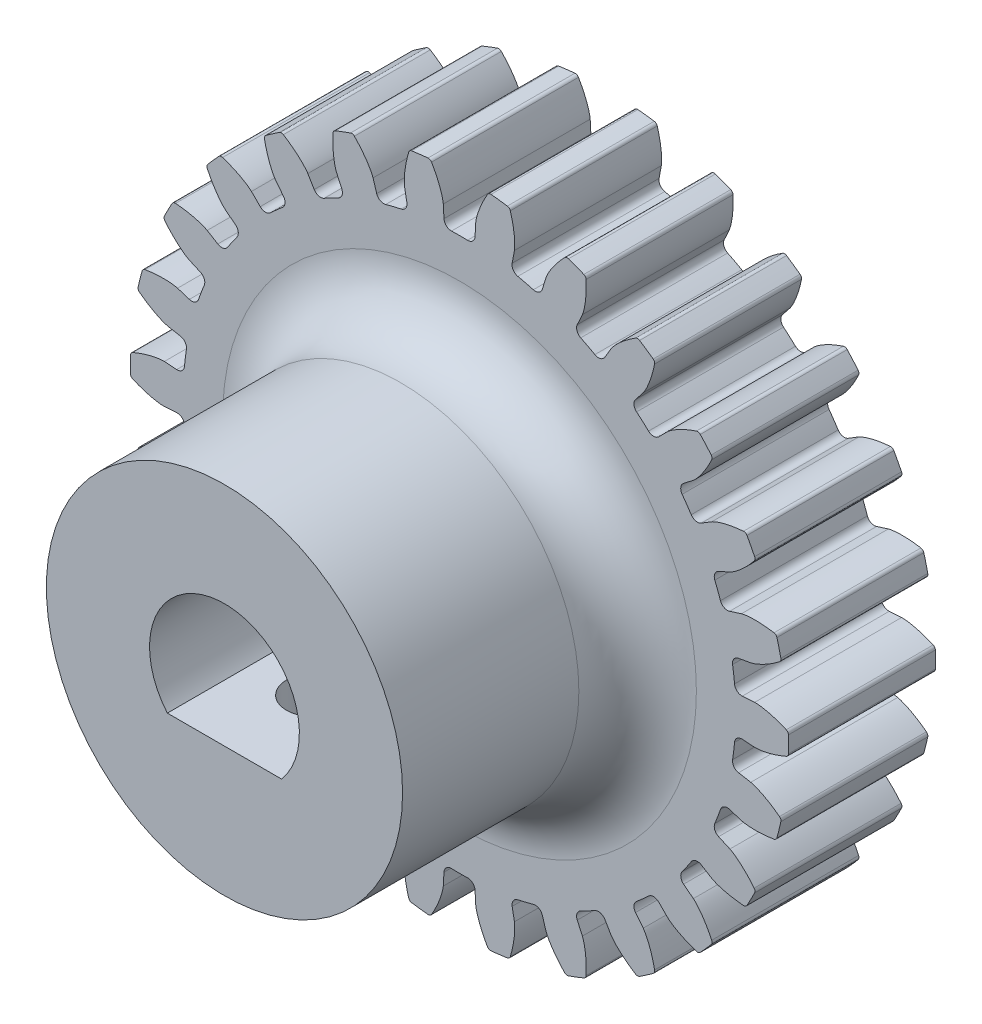
SolidWorks part; units mm, degrees
material "ABS"
ref_plane "Front" through (0, 0, 0) normal (0, 0, 1) x (1, 0, 0)
ref_plane "Top" through (0, 0, 0) normal (0, 1, 0) x (1, 0, 0)
ref_plane "Right" through (0, 0, 0) normal (1, 0, 0) x (0, 0, -1)
sketch "Sketch1" plane through (0, 0, 0) normal (0, 0, 1) x (1, 0, 0)
  circle A0 centre (0, 0) radius 14.224
  dimension "OutsideDiameter" = 28.448
extrude "Boss-Extrude1" add sketch "Sketch1" along normal blind 6.35
sketch "Sketch3" plane through (0, 0, 0) normal (0, 0, 1) x (1, 0, 0)
  line L0 (0, 0) -> (43.7181, 0) construction
  line L2 (0, 0) -> (-0.6547, 11.92) construction
  line L3 (0, 0) -> (0.6547, 11.92) construction
  line L4 (0.6547, 11.92) -> (0.7013, 12.768) construction
  line L5 (0, 0) -> (0, 61.276) construction
  line L6 (-0.6547, 11.92) -> (-0.7013, 12.768) construction
  circle A0 centre (0, 0) radius 14.224 construction
  circle A1 centre (0, 0) radius 13.208 construction
  circle A2 centre (0, 0) radius 12.7873 construction
  arc A3 (0.6547, 11.92) -> (-0.6547, 11.92) centre (0, 0) ccw construction
  arc A5 (1.2601, 14.1681) -> (-1.2601, 14.1681) centre (0, 0) ccw
  spline S0 degree 4 poles (-0.7013, 12.768) (-0.7014, 12.7703) (-0.7019, 12.7766) (-0.7031, 12.7884) (-0.7055, 12.8077) (-0.709, 12.8323) (-0.7143, 12.864) (-0.7215, 12.9013) (-0.7302, 12.9422) (-0.7407, 12.9866) (-0.752, 13.0308) (-0.7641, 13.0749) (-0.777, 13.1187) (-0.7933, 13.1717) (-0.8142, 13.2351) (-0.8403, 13.3091) (-0.872, 13.3928) (-0.9064, 13.4778) (-0.9422, 13.5612) (-0.9804, 13.6452) (-1.0189, 13.7264) (-1.061, 13.8104) (-1.1009, 13.8878) (-1.148, 13.9742) (-1.1867, 14.0438) (-1.2403, 14.1353) (-1.2727, 14.1892) (-1.3115, 14.2522) (-1.3292, 14.2801) (-1.3401, 14.2973) knots 0 0 0 0 0 0.005377 0.015084 0.028532 0.04661 0.064855 0.092111 0.119476 0.146842 0.174209 0.201575 0.228941 0.256307 0.307035 0.361767 0.4165 0.471232 0.525964 0.580697 0.635429 0.690161 0.744894 0.799626 0.854358 0.909091 0.954545 1 1 1 1 1 construction
  spline S1 degree 4 poles (-0.7013, 12.768) (-0.7014, 12.7703) (-0.7019, 12.7766) (-0.7031, 12.7884) (-0.7055, 12.8077) (-0.709, 12.8323) (-0.7143, 12.864) (-0.7215, 12.9013) (-0.7302, 12.9422) (-0.7407, 12.9866) (-0.752, 13.0308) (-0.7641, 13.0749) (-0.777, 13.1187) (-0.7933, 13.1717) (-0.8142, 13.2351) (-0.8403, 13.3091) (-0.872, 13.3928) (-0.9064, 13.4778) (-0.9422, 13.5612) (-0.9804, 13.6452) (-1.0189, 13.7264) (-1.061, 13.8104) (-1.1009, 13.8878) (-1.148, 13.9742) (-1.1867, 14.0438) (-1.2287, 14.1154) (-1.2494, 14.1503) (-1.2601, 14.1681) knots 0 0 0 0 0 0.005377 0.015084 0.028532 0.04661 0.064855 0.092111 0.119476 0.146842 0.174209 0.201575 0.228941 0.256307 0.307035 0.361767 0.4165 0.471232 0.525964 0.580697 0.635429 0.690161 0.744894 0.799626 0.854358 0.909091 0.909091 0.909091 0.909091 0.909091
  spline S2 degree 4 poles (0.7013, 12.768) (0.7014, 12.7703) (0.7019, 12.7766) (0.7031, 12.7884) (0.7055, 12.8077) (0.709, 12.8323) (0.7143, 12.864) (0.7215, 12.9013) (0.7302, 12.9422) (0.7407, 12.9866) (0.752, 13.0308) (0.7641, 13.0749) (0.777, 13.1187) (0.7933, 13.1717) (0.8142, 13.2351) (0.8403, 13.3091) (0.872, 13.3928) (0.9064, 13.4778) (0.9422, 13.5612) (0.9804, 13.6452) (1.0189, 13.7264) (1.061, 13.8104) (1.1009, 13.8878) (1.148, 13.9742) (1.1867, 14.0438) (1.2403, 14.1353) (1.2727, 14.1892) (1.3115, 14.2522) (1.3292, 14.2801) (1.3401, 14.2973) knots 0 0 0 0 0 0.005377 0.015084 0.028532 0.04661 0.064855 0.092111 0.119476 0.146842 0.174209 0.201575 0.228941 0.256307 0.307035 0.361767 0.4165 0.471232 0.525964 0.580697 0.635429 0.690161 0.744894 0.799626 0.854358 0.909091 0.954545 1 1 1 1 1 construction
  spline S3 degree 4 poles (0.7013, 12.768) (0.7014, 12.7703) (0.7019, 12.7766) (0.7031, 12.7884) (0.7055, 12.8077) (0.709, 12.8323) (0.7143, 12.864) (0.7215, 12.9013) (0.7302, 12.9422) (0.7407, 12.9866) (0.752, 13.0308) (0.7641, 13.0749) (0.777, 13.1187) (0.7933, 13.1717) (0.8142, 13.2351) (0.8403, 13.3091) (0.872, 13.3928) (0.9064, 13.4778) (0.9422, 13.5612) (0.9804, 13.6452) (1.0189, 13.7264) (1.061, 13.8104) (1.1009, 13.8878) (1.148, 13.9742) (1.1867, 14.0438) (1.2287, 14.1154) (1.2494, 14.1503) (1.2601, 14.1681) knots 0 0 0 0 0 0.005377 0.015084 0.028532 0.04661 0.064855 0.092111 0.119476 0.146842 0.174209 0.201575 0.228941 0.256307 0.307035 0.361767 0.4165 0.471232 0.525964 0.580697 0.635429 0.690161 0.744894 0.799626 0.854358 0.909091 0.909091 0.909091 0.909091 0.909091
  point P0 (0, 11.938)
  dimension "OutsideDiameter" = 28.448
  dimension "PitchCircle" = 26.416
  dimension "BaseCircle" = 25.5746
  dimension "DedendumCircle" = 23.876
sketch "DCLTBC" plane through (0, 0, 0) normal (0, 0, 1) x (1, 0, 0)
  line L0 (0, 0) -> (41.04, 0) construction
  line L1 (-0.6547, 11.92) -> (-0.7013, 12.768) construction
  line L2 (0.6547, 11.92) -> (0.7013, 12.768) construction
  line L3 (-0.6547, 11.92) -> (-0.7013, 12.768)
  line L4 (0.6547, 11.92) -> (0.7013, 12.768)
  line L5 (0, 0) -> (0, 104.9356) construction
  circle A0 centre (0, 0) radius 14.224
  circle A1 centre (0, 0) radius 13.208 construction
  circle A2 centre (0, 0) radius 12.7873 construction
  arc A3 (0.6547, 11.92) -> (-0.6547, 11.92) centre (0, 0) ccw construction
  arc A4 (0.6547, 11.92) -> (-0.6547, 11.92) centre (0, 0) ccw
  spline S0 degree 4 poles (-997.5218, -66.5121) (-10.52, 11.3394) (-0.7979, 12.1584) (-0.6668, 12.4893) (-0.7055, 12.8077) (-0.709, 12.8323) (-0.7143, 12.864) (-0.7215, 12.9013) (-0.7302, 12.9422) (-0.7407, 12.9866) (-0.752, 13.0308) (-0.7641, 13.0749) (-0.777, 13.1187) (-0.7933, 13.1717) (-0.8142, 13.2351) (-0.8403, 13.3091) (-0.872, 13.3928) (-0.9064, 13.4778) (-0.9422, 13.5612) (-0.9804, 13.6452) (-1.0189, 13.7264) (-1.061, 13.8104) (-1.1009, 13.8878) (-1.148, 13.9742) (-1.3672, 14.3683) (-2.2498, 15.7567) (10.602, -5.7239) (-517.3013, 870.6887) knots -0.722064 -0.722064 -0.722064 -0.722064 -0.722064 0.005377 0.015084 0.028532 0.04661 0.064855 0.092111 0.119476 0.146842 0.174209 0.201575 0.228941 0.256307 0.307035 0.361767 0.4165 0.471232 0.525964 0.580697 0.635429 0.690161 0.744894 0.799626 0.854358 1.929512 1.929512 1.929512 1.929512 1.929512 only from (-0.7013, 12.768) to (-1.2601, 14.1681) construction
  spline S1 degree 4 poles (997.5218, -66.5121) (10.52, 11.3394) (0.7979, 12.1584) (0.6668, 12.4893) (0.7055, 12.8077) (0.709, 12.8323) (0.7143, 12.864) (0.7215, 12.9013) (0.7302, 12.9422) (0.7407, 12.9866) (0.752, 13.0308) (0.7641, 13.0749) (0.777, 13.1187) (0.7933, 13.1717) (0.8142, 13.2351) (0.8403, 13.3091) (0.872, 13.3928) (0.9064, 13.4778) (0.9422, 13.5612) (0.9804, 13.6452) (1.0189, 13.7264) (1.061, 13.8104) (1.1009, 13.8878) (1.148, 13.9742) (1.3672, 14.3683) (2.2498, 15.7567) (-10.602, -5.7239) (517.3013, 870.6887) knots -0.722064 -0.722064 -0.722064 -0.722064 -0.722064 0.005377 0.015084 0.028532 0.04661 0.064855 0.092111 0.119476 0.146842 0.174209 0.201575 0.228941 0.256307 0.307035 0.361767 0.4165 0.471232 0.525964 0.580697 0.635429 0.690161 0.744894 0.799626 0.854358 1.929512 1.929512 1.929512 1.929512 1.929512 only from (0.7013, 12.768) to (1.2601, 14.1681) construction
  spline S2 degree 4 poles (-0.7013, 12.768) (-0.7014, 12.7703) (-0.7019, 12.7766) (-0.7031, 12.7884) (-0.7055, 12.8077) (-0.709, 12.8323) (-0.7143, 12.864) (-0.7215, 12.9013) (-0.7302, 12.9422) (-0.7407, 12.9866) (-0.752, 13.0308) (-0.7641, 13.0749) (-0.777, 13.1187) (-0.7933, 13.1717) (-0.8142, 13.2351) (-0.8403, 13.3091) (-0.872, 13.3928) (-0.9064, 13.4778) (-0.9422, 13.5612) (-0.9804, 13.6452) (-1.0189, 13.7264) (-1.061, 13.8104) (-1.1009, 13.8878) (-1.148, 13.9742) (-1.1867, 14.0438) (-1.2287, 14.1154) (-1.2494, 14.1503) (-1.2601, 14.1681) knots 0 0 0 0 0 0.005377 0.015084 0.028532 0.04661 0.064855 0.092111 0.119476 0.146842 0.174209 0.201575 0.228941 0.256307 0.307035 0.361767 0.4165 0.471232 0.525964 0.580697 0.635429 0.690161 0.744894 0.799626 0.854358 0.909091 0.909091 0.909091 0.909091 0.909091
  spline S3 degree 4 poles (0.7013, 12.768) (0.7014, 12.7703) (0.7019, 12.7766) (0.7031, 12.7884) (0.7055, 12.8077) (0.709, 12.8323) (0.7143, 12.864) (0.7215, 12.9013) (0.7302, 12.9422) (0.7407, 12.9866) (0.752, 13.0308) (0.7641, 13.0749) (0.777, 13.1187) (0.7933, 13.1717) (0.8142, 13.2351) (0.8403, 13.3091) (0.872, 13.3928) (0.9064, 13.4778) (0.9422, 13.5612) (0.9804, 13.6452) (1.0189, 13.7264) (1.061, 13.8104) (1.1009, 13.8878) (1.148, 13.9742) (1.1867, 14.0438) (1.2287, 14.1154) (1.2494, 14.1503) (1.2601, 14.1681) knots 0 0 0 0 0 0.005377 0.015084 0.028532 0.04661 0.064855 0.092111 0.119476 0.146842 0.174209 0.201575 0.228941 0.256307 0.307035 0.361767 0.4165 0.471232 0.525964 0.580697 0.635429 0.690161 0.744894 0.799626 0.854358 0.909091 0.909091 0.909091 0.909091 0.909091
  dimension "OutsideDiameter" = 28.448
  dimension "PitchCircle" = 26.416
  dimension "BaseCircle" = 25.5746
extrude "Cut-Extrude-DCLTBC" cut sketch "DCLTBC" along normal through all contours L4 S3 A0 S2 L3 A4 region at (0, 13.2044, 0)
fillet "Fillet-Tip-DCLTBC" radius 0.1588 2 edges at (1.2601, 14.1681, 3.175) (-1.2601, 14.1681, 3.175)
fillet "Fillet-Root-DCLTBC" radius 0.3176 2 edges at (-0.6547, 11.92, 3.175) (0.6547, 11.92, 3.175)
pattern_circular "CirPattern-DCLTBC" count 26 over 360 about axis through (0, 0, 6.35) along (0, 0, 1) of "Cut-Extrude-DCLTBC", "Fillet-Tip-DCLTBC", "Fillet-Root-DCLTBC"
sketch "DCGTBC" [suppressed] plane through (0, 0, 0) normal (0, 0, 1) x (1, 0, 0)
  line L0 (0, 0) -> (41.04, 0) construction
  line L1 (-37.3224, 3.2653) -> (0, 0) construction
  line L2 (0, 0) -> (37.3224, 3.2653) construction
  line L3 (0, 0) -> (-16.5124, 0)
  line L5 (0, 0) -> (0, 104.9356) construction
  circle A0 centre (0, 0) radius 38.608
  circle A1 centre (0, 0) radius 38.1 construction
  circle A2 centre (0, 0) radius 36.8864 construction
  arc A3 (0.1846, 37.4645) -> (-0.1846, 37.4645) centre (0, 0) ccw construction
  arc A11 (37.3224, 3.2653) -> (-37.3224, 3.2653) centre (0, 0) ccw
  spline S4 degree 4 poles (999.1092, -9.1639) (9.2917, 35.7604) (0.2917, 36.1338) (0.1647, 36.5321) (0.1834, 36.9323) (0.1852, 36.961) (0.188, 36.9982) (0.192, 37.0421) (0.197, 37.0904) (0.2032, 37.143) (0.21, 37.1956) (0.2175, 37.2482) (0.2254, 37.3006) (0.2357, 37.3641) (0.2489, 37.4405) (0.2657, 37.53) (0.2863, 37.6318) (0.309, 37.7359) (0.3327, 37.8385) (0.3583, 37.9426) (0.3842, 38.0436) (0.4127, 38.1489) (0.4399, 38.2463) (0.4722, 38.3558) (0.6183, 38.8417) (1.2009, 40.5477) (-6.8048, 15.7351) (309.5446, 989.6637) knots -0.780323 -0.780323 -0.780323 -0.780323 -0.780323 0.005377 0.015084 0.028532 0.04661 0.064855 0.092111 0.119476 0.146842 0.174209 0.201575 0.228941 0.256307 0.307035 0.361767 0.4165 0.471232 0.525964 0.580697 0.635429 0.690161 0.744894 0.799626 0.854358 1.89102 1.89102 1.89102 1.89102 1.89102 only from (0.1817, 36.886) to (0.5498, 38.6041) construction
  spline S5 degree 4 poles (-999.1092, -9.1639) (-9.2917, 35.7604) (-0.2917, 36.1338) (-0.1647, 36.5321) (-0.1834, 36.9323) (-0.1852, 36.961) (-0.188, 36.9982) (-0.192, 37.0421) (-0.197, 37.0904) (-0.2032, 37.143) (-0.21, 37.1956) (-0.2175, 37.2482) (-0.2254, 37.3006) (-0.2357, 37.3641) (-0.2489, 37.4405) (-0.2657, 37.53) (-0.2863, 37.6318) (-0.309, 37.7359) (-0.3327, 37.8385) (-0.3583, 37.9426) (-0.3842, 38.0436) (-0.4127, 38.1489) (-0.4399, 38.2463) (-0.4722, 38.3558) (-0.6183, 38.8417) (-1.2009, 40.5477) (6.8048, 15.7351) (-309.5446, 989.6637) knots -0.780323 -0.780323 -0.780323 -0.780323 -0.780323 0.005377 0.015084 0.028532 0.04661 0.064855 0.092111 0.119476 0.146842 0.174209 0.201575 0.228941 0.256307 0.307035 0.361767 0.4165 0.471232 0.525964 0.580697 0.635429 0.690161 0.744894 0.799626 0.854358 1.89102 1.89102 1.89102 1.89102 1.89102 only from (-0.1817, 36.886) to (-0.5498, 38.6041) construction
  spline S6 degree 4 poles (0.1817, 36.886) (0.1818, 36.8886) (0.1819, 36.8959) (0.1824, 36.9097) (0.1834, 36.9323) (0.1852, 36.961) (0.188, 36.9982) (0.192, 37.0421) (0.197, 37.0904) (0.2032, 37.143) (0.21, 37.1956) (0.2175, 37.2482) (0.2254, 37.3006) (0.2357, 37.3641) (0.2489, 37.4405) (0.2657, 37.53) (0.2863, 37.6318) (0.309, 37.7359) (0.3327, 37.8385) (0.3583, 37.9426) (0.3842, 38.0436) (0.4127, 38.1489) (0.4399, 38.2463) (0.4722, 38.3558) (0.4989, 38.4444) (0.5279, 38.5364) (0.5423, 38.5812) (0.5498, 38.6041) knots 0 0 0 0 0 0.005377 0.015084 0.028532 0.04661 0.064855 0.092111 0.119476 0.146842 0.174209 0.201575 0.228941 0.256307 0.307035 0.361767 0.4165 0.471232 0.525964 0.580697 0.635429 0.690161 0.744894 0.799626 0.854358 0.909091 0.909091 0.909091 0.909091 0.909091
  spline S7 degree 4 poles (-0.1817, 36.886) (-0.1818, 36.8886) (-0.1819, 36.8959) (-0.1824, 36.9097) (-0.1834, 36.9323) (-0.1852, 36.961) (-0.188, 36.9982) (-0.192, 37.0421) (-0.197, 37.0904) (-0.2032, 37.143) (-0.21, 37.1956) (-0.2175, 37.2482) (-0.2254, 37.3006) (-0.2357, 37.3641) (-0.2489, 37.4405) (-0.2657, 37.53) (-0.2863, 37.6318) (-0.309, 37.7359) (-0.3327, 37.8385) (-0.3583, 37.9426) (-0.3842, 38.0436) (-0.4127, 38.1489) (-0.4399, 38.2463) (-0.4722, 38.3558) (-0.4989, 38.4444) (-0.5279, 38.5364) (-0.5423, 38.5812) (-0.5498, 38.6041) knots 0 0 0 0 0 0.005377 0.015084 0.028532 0.04661 0.064855 0.092111 0.119476 0.146842 0.174209 0.201575 0.228941 0.256307 0.307035 0.361767 0.4165 0.471232 0.525964 0.580697 0.635429 0.690161 0.744894 0.799626 0.854358 0.909091 0.909091 0.909091 0.909091 0.909091
  dimension "D1" = 5
  dimension "D2" = 5
  dimension "OutsideDiameter" = 28.448
  dimension "PitchCircle" = 26.416
  dimension "BaseCircle" = 25.5746
extrude "Cut-Extrude-DCGTBC" [suppressed] cut sketch "DCGTBC" along normal through all
fillet "Fillet-Tip-DCGTBC" [suppressed] radius 0.1588
pattern_circular "CirPattern-DCGTBC" [suppressed] count 26 over 360 of bodies 112
sketch "Sketch4" plane through (0, 0, 6.35) normal (0, 0, 1) x (1, 0, 0)
  line L0 (-2.4692, -2.0955) -> (2.4692, -2.0955)
  arc A0 (2.4692, -2.0955) -> (-2.4692, -2.0955) centre (0, 0) ccw
  circle A1 centre (0, 0) radius 5.1594
  point P3 (0, 3.2385)
  dimension "D1" = 6.477
  dimension "D3" = 10.3187
  dimension "D2" = 5.334
extrude "Cut-Extrude2" cut sketch "Sketch4" against normal through all contours L0 A0 | A1 A0 L0 region at (0, 0.3457, 6.35) region at (-5.0134, 0, 6.35)
sketch "Sketch5" plane through (0, 0, 6.35) normal (0, 0, 1) x (1, 0, 0)
  line L0 (-2.4692, -2.0955) -> (2.4692, -2.0955) construction
  line L1 (-2.4692, -2.0955) -> (2.4692, -2.0955)
  circle A0 centre (0, 0) radius 7.6994
  circle A1 centre (0, 0) radius 5.1594 construction
  arc A2 (2.4692, -2.0955) -> (-2.4692, -2.0955) centre (0, 0) ccw construction
  arc A3 (2.4692, -2.0955) -> (-2.4692, -2.0955) centre (0, 0) ccw
  dimension "D1" = 2.54
extrude "Boss-Extrude2" add sketch "Sketch5" along normal blind 10.16
fillet "Fillet1" radius 2.54 1 edges at (7.6994, 0, 6.35)
ref_plane "Plane1" through (0, -7.6994, 16.51) normal (0, -1, 0) x (-1, 0, 0)
hole_wizard "#4-40 Tapped Hole1" positions "Sketch8" profile "Sketch7" tap size "#4-40" standard "ANSI Inch" end condition up to next
sketch "Sketch8" plane through (0, -7.6994, 16.51) normal (0, -1, 0) x (-1, 0, 0)
  line L0 (0, 0) -> (0, 7.62) construction
  line L2 (-7.6994, 7.62) -> (7.6994, 7.62) construction
  line L3 (-7.6994, 0) -> (7.6994, 0) construction
  point P12 (0, 3.81)
sketch "Sketch7" plane through (0, -7.6994, 12.7) normal (1, 0, 0) x (0, 0, -1)
  line L0 (0, 0) -> (0, 5.6039)
  line L1 (0, 5.6039) -> (1.1303, 5.6039)
  line L2 (1.1303, 5.6039) -> (1.1303, 0.5328)
  line L3 (1.1303, 0.5328) -> (1.7653, 0)
  line L5 (1.7653, 0) -> (0, 0)
  line L6 (-1.1303, 0.5328) -> (-1.7653, 0) construction
  line L11 (0, -6.35) -> (0, 107.95) construction
  dimension "Thru Tap Drill Dia." = 2.2606
  dimension "Thru Tap Drill Depth" = 5.6039
  dimension "Near C'Sink Dia." = 3.5306
  dimension "Near C'Sink Angle" = 100
cosmetic thread "Hole Thread1" parameters "D2"=2.8448
equation "\"DiametralPitch\"= 25'Diametral Pitch"
equation "\"NumTeeth\"= 26'Number of Teeth"
equation "\"PressureAngle\"= 14.5deg'Pressure Angle"
equation "\"Addendum\"= 1 / \"DiametralPitch\"'Addendum"
equation "\"Dedendum\"= 1.25 / \"DiametralPitch\"'Dedendum"
equation "\"WorkingDepth\"= 2 / \"DiametralPitch\"'Working Depth - here for REF (Not used in building model)"
equation "\"WholeDepth\"= 2.25 / \"DiametralPitch\"'Whole Depth - here for REF (Not used in building model)"
equation "\"Clearance\"= .25 / \"DiametralPitch\"'Clearance"
equation "\"CircularPitch\"= pi / \"DiametralPitch\"'Circular Pitch - here for REF (Not used in building model)"
equation "\"PitchCircle\"= \"NumTeeth\" / \"DiametralPitch\"'Pitch Circle - or - Pitch Diameter"
equation "\"OutsideDiameter\"= ( \"NumTeeth\" + 2 ) / \"DiametralPitch\"'Outside Diameter"
equation "\"Fillet_Root\"= \"Clearance\" * cos ( \"PressureAngle\" ) * tan ( ( 90 + \"PressureAngle\" ) / 2 ) 'Fillet Root"
equation "\"AddendumCircle\"= \"PitchCircle\" + ( 2 * \"Addendum\" )'Addendum Circle - or - Addendum Diameter"
equation "\"DedendumCircle\"= \"PitchCircle\" - ( 2 * \"Dedendum\" )'Dedendum Circle - or - Dedendum Diameter"
equation "\"BaseCircle\"= \"PitchCircle\" * cos ( \"PressureAngle\" )'Base Circle - Base Diameter"
equation "\"PitchAngle\"= 360deg / \"NumTeeth\"'Pitch Angle"
equation "\"Alpha\"= sqr ( \"PitchCircle\" ^ 2 - \"BaseCircle\" ^ 2 ) / \"BaseCircle\" * 180 / PI - \"PressureAngle\"'Alpha - Used for Calculating Beta"
equation "\"Beta\"= ( \"PitchAngle\" / 4 - ( \"Alpha\" - 90 ) )'Beta - Used in definition of the parameters for the parametric equation driven curve"
equation "\"Gamma\"= ( \"PitchAngle\" / 4 - ( \"Alpha\" + 90 ) )'Gamma - Used in definition of the parameters for the parametric equation driven curve"
equation "\"Phi\"= sqr ( ( \"AddendumCircle\" / 2 ) ^ 2 - ( \"BaseCircle\" / 2 ) ^ 2 ) / ( \"BaseCircle\" / 2 )'Phi - Used in definition of the parameters for the parametric equation driven curve"
equation "\"DCGTBC\"= iif ( \"DedendumCircle\" > \"BaseCircle\" , \"unsuppressed\" , \"suppressed\" )'if Dedendum Circle IS GREATER THAN BaseCircle THEN UnsuppressORSuppress FEATURE"
equation "\"DCLTBC\"= iif ( \"DedendumCircle\" - .002 > \"BaseCircle\" , \"suppressed\" , \"unsuppressed\" )'if Dedendum Circle - .002 IS GREATER THAN BaseCircle THEN SuppressORUnsuppress FEATURE"
equation "\"Cut-Extrude-DCGTBC\"= iif ( \"DedendumCircle\" > \"BaseCircle\" , \"unsuppressed\" , \"suppressed\" )'if Dedendum Circle IS GREATER THAN BaseCircle THEN UnsuppressORSuppress FEATURE"
equation "\"Cut-Extrude-DCLTBC\"= iif ( \"DedendumCircle\" - .002 > \"BaseCircle\" , \"suppressed\" , \"unsuppressed\" )'if Dedendum Circle - .002 IS GREATER THAN BaseCircle THEN SuppressORUnsuppress FEATURE"
equation "\"CirPattern-DCGTBC\"= iif ( \"DedendumCircle\" > \"BaseCircle\" , \"unsuppressed\" , \"suppressed\" )'if Dedendum Circle IS GREATER THAN BaseCircle THEN UnsuppressORSuppress FEATURE"
equation "\"CirPattern-DCLTBC\"= iif ( \"DedendumCircle\" - .002 > \"BaseCircle\" , \"suppressed\" , \"unsuppressed\" )'if Dedendum Circle - .002 IS GREATER THAN BaseCircle THEN SuppressORUnsuppress FEATURE"
equation "\"Fillet-Tip-DCGTBC\"= iif ( \"DedendumCircle\" > \"BaseCircle\" , \"unsuppressed\" , \"suppressed\" )'if Dedendum Circle IS GREATER THAN BaseCircle THEN UnsuppressORSuppress FEATURE"
equation "\"Fillet-Tip-DCLTBC\"= iif ( \"DedendumCircle\" - .002 > \"BaseCircle\" , \"suppressed\" , \"unsuppressed\" )'if Dedendum Circle - .002 IS GREATER THAN BaseCircle THEN SuppressORUnsuppress FEATURE"
equation "\"Fillet-Root-DCLTBC\"= iif ( \"DedendumCircle\" - .002 > \"BaseCircle\" , \"suppressed\" , \"unsuppressed\" )'if Dedendum Circle - .002 IS GREATER THAN BaseCircle THEN SuppressORUnsuppress FEATURE"
equation "\"D1@CirPattern-DCGTBC\"= \"NumTeeth\"'Number of Teeth"
equation "\"D1@CirPattern-DCLTBC\"= \"NumTeeth\"'Number of Teeth"
equation "\"D1@Fillet-Tip-DCGTBC\"= \"Fillet_Root\" / 2 'Tip Rad For Large No of Teeth"
equation "\"D1@Fillet-Tip-DCLTBC\"=\"Fillet_Root\" / 2'Tip Rad For Small No of Teeth"
equation "\"D1@Fillet-Root-DCLTBC\"= \"Fillet_Root\"'Fillet Root"
